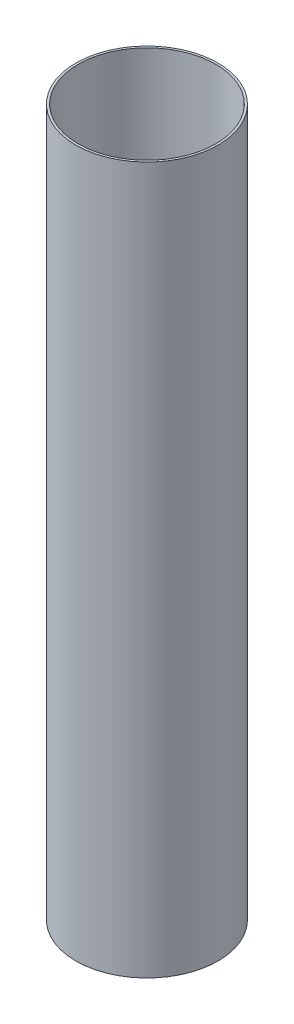
SolidWorks part; units mm, degrees
ref_plane "Front Plane" through (0, 0, 0) normal (0, 0, 1) x (1, 0, 0)
ref_plane "Top Plane" through (0, 0, 0) normal (0, 1, 0) x (1, 0, 0)
ref_plane "Right Plane" through (0, 0, 0) normal (1, 0, 0) x (0, 0, -1)
sketch "Sketch1" plane through (0, 0, 0) normal (0, 1, 0) x (1, 0, 0)
  circle A0 centre (0, 0) radius 51.1048
  circle A1 centre (0, 0) radius 49.53
  dimension "D1" = 102.2096
  dimension "D2" = 99.06
extrude "Boss-Extrude1" add sketch "Sketch1" along normal blind 508
equation "\"Body_Tube_OD\"= 4.024in"
equation "\"Body_Tube_ID\"= 3.90in"
equation "\"D1@Sketch1\"=\"Body_Tube_OD\""
equation "\"D2@Sketch1\"=\"Body_Tube_ID\""
equation "\"Fwd_Section_Length\" = 20in"
equation "\"D1@Boss-Extrude1\"=\"Fwd_Section_Length\""
